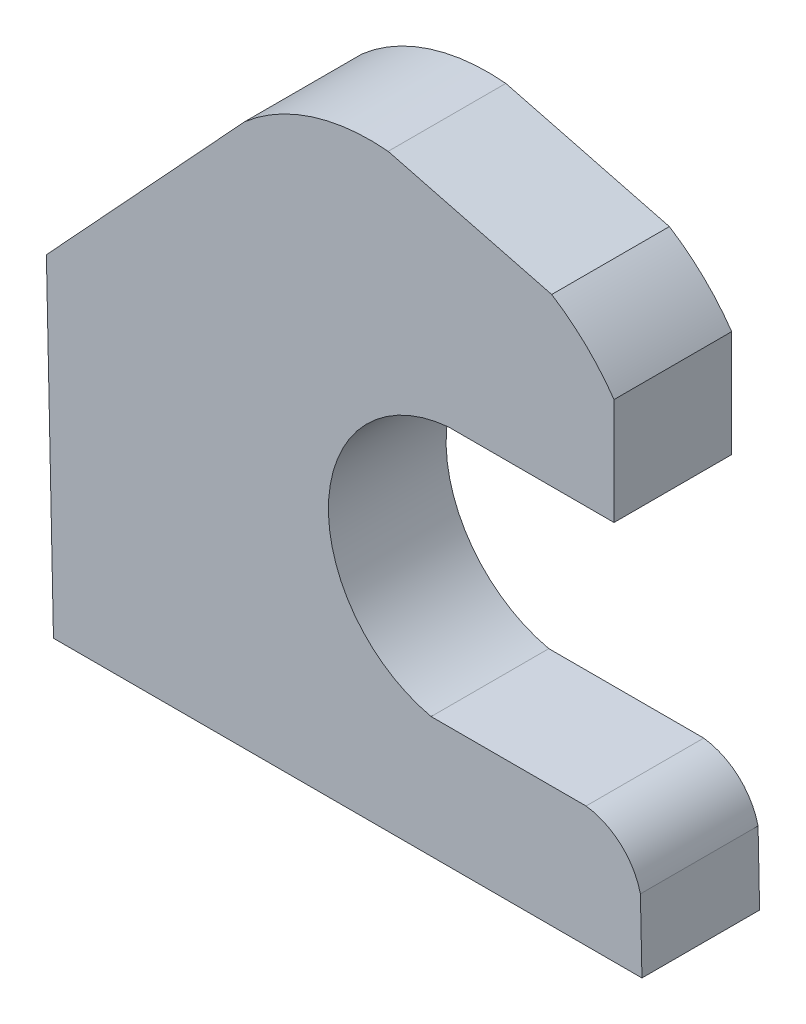
SolidWorks part; units mm, degrees
ref_plane "Ön Düzlem" through (0, 0, 0) normal (0, 0, 1) x (1, 0, 0)
ref_plane "Üst Düzlem" through (0, 0, 0) normal (0, 1, 0) x (1, 0, 0)
ref_plane "Sağ Düzlem" through (0, 0, 0) normal (1, 0, 0) x (0, 0, -1)
sketch "Çizim1" plane through (0, 0, 0) normal (0, 0, 1) x (1, 0, 0)
  line L0 (0, 0) -> (218.5, 0)
  line L1 (302.5, 50) -> (302.5, 0) construction
  line L2 (360, 0) -> (449, 0)
  line L3 (550.0826, 97.3608) -> (550.0826, 589.3608) construction
  line L4 (449, 0) -> (446, 139) construction
  line L5 (432.909, 160) -> (367.0814, 160)
  line L6 (374.5137, 275.2653) -> (436, 275.2653) construction
  line L7 (415.2252, 333.8789) -> (346.909, 351.5089) construction
  line L8 (171.8289, 213.8793) -> (287.7727, 339.2159)
  line L9 (53.1497, 187.1774) -> (53.1497, 80.8624)
  line L10 (0, 0) -> (53.1497, 80.8624)
  line L11 (333.5, 0) -> (360, 0)
  line L12 (374.5137, 270.2653) -> (434.7981, 270.2653)
  line L13 (374.5137, 270.2653) -> (436, 270.2653) construction
  line L14 (458.9977, 0.2158) -> (455.9977, 139.2158)
  line L15 (449, 0) -> (458.9977, 0.2158)
  line L16 (434.7981, 270.2653) -> (444.7981, 270.2653)
  line L17 (444.7981, 270.2653) -> (444.7981, 315.517)
  line L18 (418.3092, 340.932) -> (348.8081, 358.8678)
  line L20 (417.1243, 341.2378) -> (348.8081, 358.8678) construction
  arc A0 (245, 0) -> (360, 0) centre (302.5, -8.0625) cw construction
  arc A1 (446, 139) -> (420, 160) centre (419.4413, 132.713) ccw construction
  arc A2 (374.5137, 275.2653) -> (367.0814, 160) centre (379.3462, 217.0814) ccw construction
  arc A3 (434.7981, 270.2653) -> (440.201, 308.7194) centre (264.9649, 313.7338) ccw construction
  arc A4 (440.201, 308.7194) -> (415.2252, 333.8789) centre (368.7361, 262.7527) ccw construction
  arc A5 (346.909, 351.5089) -> (287.7727, 339.2159) centre (330.696, 281.1162) ccw construction
  arc A6 (113.8141, 180.7269) -> (171.8289, 213.8793) centre (67.1241, 329.7694) ccw
  arc A7 (53.1497, 187.1774) -> (113.8141, 180.7269) centre (92.6596, 270.2653) ccw
  arc A8 (218.5, 0) -> (333.5, 0) centre (276, -8.0625) cw
  arc A9 (374.5137, 270.2653) -> (367.0814, 160) centre (379.3462, 214.5564) ccw
  arc A10 (455.9977, 139.2158) -> (432.909, 160) centre (429.4389, 132.9288) ccw
  arc A11 (444.7981, 315.517) -> (418.3092, 340.932) centre (368.7361, 262.7527) ccw
  arc A12 (446.5929, 312.8308) -> (419.3833, 340.2405) centre (368.7361, 262.7527) ccw construction
  arc A13 (287.7727, 339.2159) -> (348.8081, 358.8678) centre (341.1816, 277.9456) cw
  point P10 (360, 162)
  point P11 (357, 271)
  dimension "D20" = 58.3842
  dimension "D1" = 245
  dimension "D2" = 360
  dimension "D3" = 50
  dimension "D4" = 449
  dimension "D7" = 446
  dimension "D5" = 139
  dimension "D6" = 420
  dimension "D8" = 160
  dimension "D9" = 162
  dimension "D10" = 360
  dimension "D11" = 271
  dimension "D12" = 357
  dimension "D13" = 275.2653
  dimension "D14" = 436
  dimension "D15" = 146.5
  dimension "D17" = 173
  dimension "D18" = 115
  dimension "D21" = 58.6136
  dimension "D22" = 63.6136
  dimension "D24" = 10
  dimension "D19" = 5
  dimension "D23" = 10
  dimension "D26" = 7.6
  dimension "D25" = 7.6
base flange "Taban-Flanş1" sketch "Çizim1" thickness 50 reverse thickness direction yes parameters "D1"=10
sketch "Çizim2" plane through (0, 0, 50) normal (0, 0, 1) x (1, 0, 0)
  line L3 (206.6006, 108.5804) -> (203.5871, 248.2103)
  line L5 (458.9977, 0.2158) -> (455.9977, 139.2158) construction
  line L6 (456.6589, 108.5804) -> (206.6006, 108.5804)
  line L7 (458.9977, 0.2158) -> (455.9977, 139.2158) construction
  line L8 (333.5, 0) -> (449, 0) construction
  line L9 (330.9547, 358.5804) -> (330.9547, 108.5804) construction
  line L10 (287.7727, 339.2159) -> (171.8289, 213.8793) construction
  line L11 (203.5871, 248.2103) -> (171.8289, 213.8793)
  line L23 (53.1497, 80.8624) -> (0, 0)
  line L24 (53.1497, 187.1774) -> (53.1497, 80.8624)
  line L25 (287.7727, 339.2159) -> (171.8289, 213.8793)
  line L26 (418.3092, 340.932) -> (348.8081, 358.8678)
  line L27 (444.7981, 270.2653) -> (444.7981, 315.517)
  line L28 (374.5137, 270.2653) -> (444.7981, 270.2653)
  line L29 (432.909, 160) -> (367.0814, 160)
  line L30 (458.9977, 0.2158) -> (455.9977, 139.2158)
  line L31 (449, 0) -> (458.9977, 0.2158)
  line L32 (333.5, 0) -> (449, 0)
  line L33 (0, 0) -> (218.5, 0)
  line L34 (53.1497, 80.8624) -> (0, 0)
  line L35 (53.1497, 187.1774) -> (53.1497, 80.8624)
  line L36 (203.5871, 248.2103) -> (171.8289, 213.8793)
  line L41 (458.9977, 0.2158) -> (456.6589, 108.5804)
  line L42 (449, 0) -> (458.9977, 0.2158)
  line L43 (333.5, 0) -> (449, 0)
  line L44 (0, 0) -> (218.5, 0)
  arc A9 (53.1497, 187.1774) -> (113.8141, 180.7269) centre (92.6596, 270.2653) ccw
  arc A10 (113.8141, 180.7269) -> (171.8289, 213.8793) centre (67.1241, 329.7694) ccw
  arc A11 (348.8081, 358.8678) -> (287.7727, 339.2159) centre (341.1816, 277.9456) ccw
  arc A12 (444.7981, 315.517) -> (418.3092, 340.932) centre (368.7361, 262.7527) ccw
  arc A13 (374.5137, 270.2653) -> (367.0814, 160) centre (379.3462, 214.5564) ccw
  arc A14 (455.9977, 139.2158) -> (432.909, 160) centre (429.4389, 132.9288) ccw
  arc A15 (333.5, 0) -> (218.5, 0) centre (276, -8.0625) ccw
  arc A16 (53.1497, 187.1774) -> (113.8141, 180.7269) centre (92.6596, 270.2653) ccw
  arc A17 (113.8141, 180.7269) -> (171.8289, 213.8793) centre (67.1241, 329.7694) ccw
  arc A22 (333.5, 0) -> (218.5, 0) centre (276, -8.0625) ccw
  dimension "D1" = 250
  dimension "D2" = 250
  dimension "D3" = 0
extrude "Kes-Ekstrüzyon1" cut sketch "Çizim2" against normal through all both and the other way through all
sketch "Büküm-Çizgileri1" [suppressed] plane through (0, 0, 0) normal (0, 1, 0) x (1, 0, 0)
sketch "Sınırlandırma-Kutusu1" [suppressed] plane through (0, 0, 0) normal (0, 1, 0) x (1, 0, 0)
sheet metal parameters "Sac-Levha1" thickness 50 parameters "D1"=10
flat pattern "Düz-Çoğaltma1" [suppressed]
sketch "Büküm-Çizgileri2" plane through (0, 0, 0) normal (0, 1, 0) x (1, 0, 0)
sketch3d "Sınırlandırma-Kutusu2" [suppressed]
  line L0 (-92.6596, -270.2653, 0) -> (366.3381, -270.2653, 0) construction
  line L1 (-92.6596, 88.961, 0) -> (366.3381, 88.961, 0) construction
  line L2 (-92.6596, -270.2653, 0) -> (-92.6596, 88.961, 0) construction
  line L3 (366.3381, -270.2653, 0) -> (366.3381, 88.961, 0) construction
sheet metal parameters "Sac-Levha2" thickness 50 parameters "D1"=10
flat pattern "Düz-Çoğaltma1"
sketch "Büküm-Çizgileri2" plane through (0, 0, 0) normal (0, 1, 0) x (1, 0, 0)
sketch3d "Sınırlandırma-Kutusu2" [suppressed]
  line L0 (-358.538, 91.3544, 0) -> (-363.9993, -161.6849, 0) construction
  line L1 (-108.5962, 85.96, 0) -> (-114.0575, -167.0793, 0) construction
  line L2 (-358.538, 91.3544, 0) -> (-108.5962, 85.96, 0) construction
  line L3 (-363.9993, -161.6849, 0) -> (-114.0575, -167.0793, 0) construction
